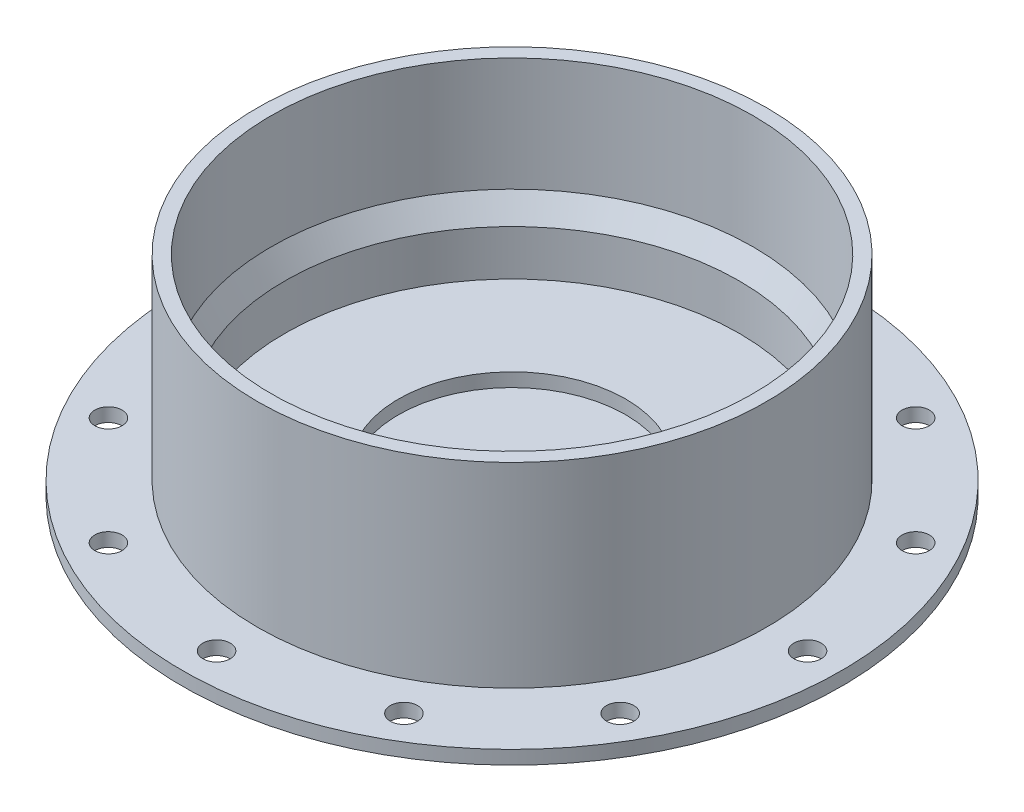
SolidWorks part; units mm, degrees
ref_plane "Front Plane" through (0, 0, 0) normal (0, 0, 1) x (1, 0, 0)
ref_plane "Top Plane" through (0, 0, 0) normal (0, 1, 0) x (1, 0, 0)
ref_plane "Right Plane" through (0, 0, 0) normal (1, 0, 0) x (0, 0, -1)
sketch "Sketch1" plane through (0, 0, 0) normal (1, 0, 0) x (0, 0, -1)
  line L0 (0, 0) -> (25, 0) construction
  line L1 (25, 0) -> (25, -3)
  line L2 (25, 0) -> (50, 0)
  line L3 (50, 0) -> (50, 10)
  line L5 (56, 40) -> (56, -3)
  line L6 (56, -3) -> (25, -3) construction
  line L7 (0, 0) -> (0, 10) construction
  line L8 (25, -3) -> (0, -3)
  line L9 (0, -3) -> (0, -6)
  line L10 (0, -6) -> (56, -6)
  line L11 (56, -6) -> (56, -3)
  line L12 (50, 10) -> (53, 15)
  line L13 (53, 15) -> (53, 40)
  line L14 (53, 40) -> (56, 40)
  point P13 (54.5, 40)
  dimension "D1" = 25
  dimension "D2" = 10
  dimension "D3" = 50
  dimension "D4" = 40
  dimension "D5" = 3
  dimension "D6" = 3
  dimension "D7" = 3
  dimension "D8" = 3
  dimension "D9" = 5
  dimension "D10" = 10
revolve "Revolve1" add sketch "Sketch1" angle 360 about L7
sketch "Sketch2" plane through (0, 0, 0) normal (0, 1, 0) x (1, 0, 0)
  line L3 (0, 0) -> (0, 65) construction
  circle A4 centre (0, 65) radius 3
  circle A8 centre (0, 0) radius 72.5
  circle A9 centre (32.5, 56.2917) radius 3
  circle A10 centre (56.2917, 32.5) radius 3
  circle A11 centre (65, 0) radius 3
  circle A12 centre (56.2917, -32.5) radius 3
  circle A13 centre (32.5, -56.2917) radius 3
  circle A14 centre (0, -65) radius 3
  circle A15 centre (-32.5, -56.2917) radius 3
  circle A16 centre (-56.2917, -32.5) radius 3
  circle A17 centre (-65, 0) radius 3
  circle A18 centre (-56.2917, 32.5) radius 3
  circle A19 centre (-32.5, 56.2917) radius 3
  point P29 (0, 0)
  dimension "D1" = 6
  dimension "D2" = 145
  dimension "D3" = 65
  dimension "D4" = 12
extrude "Boss-Extrude1" add sketch "Sketch2" along normal blind 3 from surface contours A4 region at (0, 0, 0) starting at face at (0, -6, -56)
